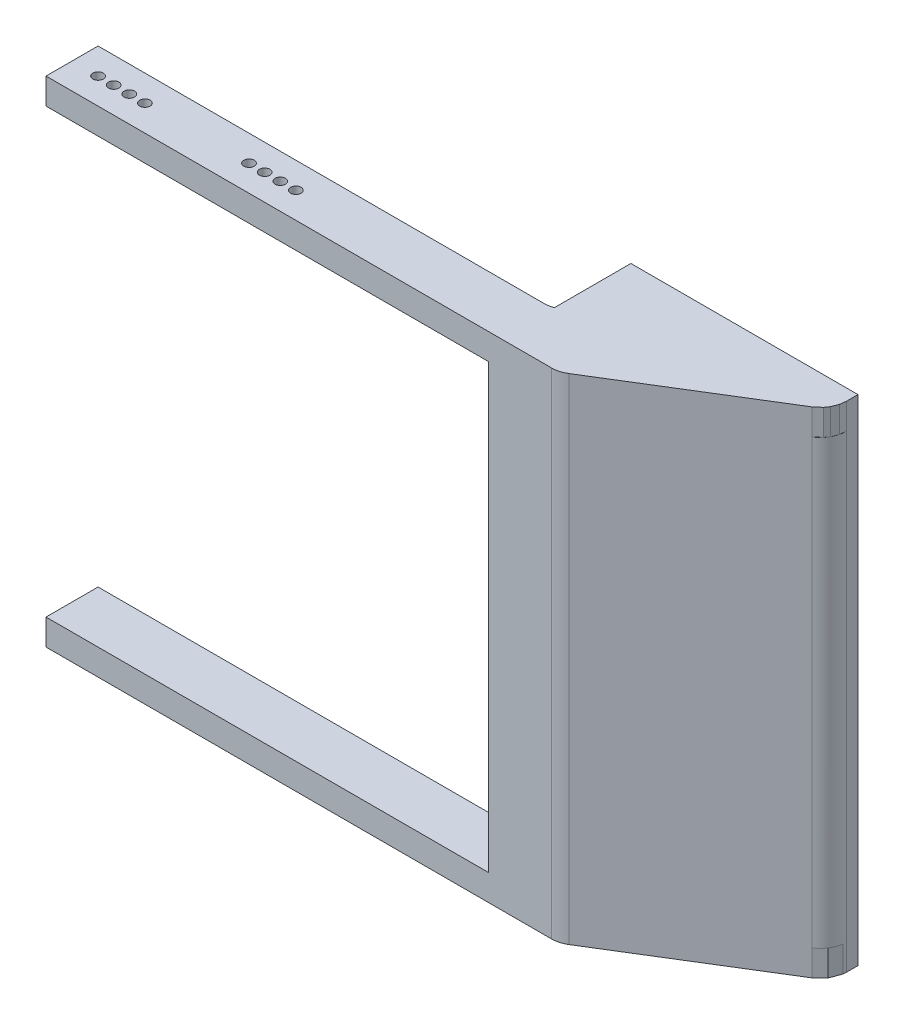
SolidWorks part; units mm, degrees
other "Marquage1"
sketch "Esquisse6" plane through (-75, 0, -38.2843) normal (-0.024, -0.0063, -0.9997) x (-0.9942, -0.1051, 0.0245)
ref_plane "Front Plane" through (0, 0, 0) normal (0, 0, 1) x (1, 0, 0)
ref_plane "Top Plane" through (0, 0, 0) normal (0, 1, 0) x (1, 0, 0)
ref_plane "Right Plane" through (0, 0, 0) normal (1, 0, 0) x (0, 0, -1)
sketch "Sketch1" plane through (0, 0, 0) normal (0, 1, 0) x (1, 0, 0)
  line L0 (-55, 0) -> (55, 0) construction
  line L1 (30, 0) -> (-75, 0)
  line L4 (-75, 0) -> (-75, 10)
  line L5 (30, 10) -> (55.9808, 25)
  line L6 (55.9808, 25) -> (55.9808, 20)
  line L7 (55.9808, 20) -> (28.4498, 3.0365)
  line L8 (30, 10) -> (12.5, 25)
  line L9 (12.5, 25) -> (12.5, 20)
  line L10 (12.5, 20) -> (24.1667, 10)
  line L11 (28.4498, 3.0365) -> (23.5217, 0)
  line L12 (-75, 10) -> (24.1667, 10)
  line L13 (23.5217, 0) -> (-75, 0)
  line L14 (24.1667, 10) -> (30, 10)
  dimension "D10" = 10
  dimension "D1" = 30
  dimension "D2" = 30
  dimension "D3" = 75
  dimension "D4" = 10
  dimension "D5" = 20
  dimension "D6" = 30
  dimension "D7" = 5
  dimension "D8" = 20
  dimension "D9" = 5
  dimension "D11" = 109.399
extrude "Boss-Extrude3" add sketch "Sketch1" along normal blind 95 contours L4 L12 L10 L9 L8 L5 L6 L7 L11 L13
fillet "Fillet8" radius 5 1 edges at (24.1667, 47.5, -10)
fillet "Fillet9" radius 5 2 edges at (55.9808, 47.5, -20) (12.5, 47.5, -20)
fillet "Fillet10" radius 5 1 edges at (23.5217, 47.5, 0)
sketch "Esquisse3" plane through (0, 0, -10) normal (0, 0, -1) x (-1, 0, 0)
  line L0 (75, 95) -> (75, 0) construction
  line L1 (75, 5) -> (45, 5)
  line L2 (75, 5) -> (75, 90)
  line L3 (75, 90) -> (45, 90)
  line L4 (45, 5) -> (45, 90)
  line L5 (75, 0) -> (-10.6504, 0) construction
  line L6 (75, 95) -> (-10.6504, 95) construction
  dimension "D1" = 5
  dimension "D2" = 5
  dimension "D3" = 30
extrude "Enlèv. mat.-Extru.1" cut sketch "Esquisse3" against normal through all contours L2 L1 L4 L3
sketch "Esquisse5" plane through (0, 0, -10) normal (0, 0, -1) x (-1, 0, 0)
  line L1 (45, 5) -> (35, 5)
  line L2 (45, 5) -> (45, 65)
  line L3 (45, 65) -> (35, 65)
  line L4 (35, 5) -> (35, 65)
  dimension "D1" = 10
extrude "Enlèv. mat.-Extru.2" cut sketch "Esquisse5" against normal through all contours L2 L1 L4 L3
sketch "Esquisse14" plane through (0, 0, -10) normal (0, 0, -1) x (-1, 0, 0)
  line L0 (45, 65) -> (35, 65) construction
  line L1 (45, 90) -> (35, 90)
  line L2 (45, 90) -> (45, 65)
  line L3 (45, 65) -> (35, 65)
  line L4 (35, 90) -> (35, 65)
extrude "Enlèv. mat.-Extru.7" cut sketch "Esquisse14" against normal through all
sketch "Esquisse15" plane through (0, 0, -10) normal (0, 0, -1) x (-1, 0, 0)
  line L1 (35, 90) -> (5, 90)
  line L2 (35, 90) -> (35, 5)
  line L3 (35, 5) -> (5, 5)
  line L4 (5, 90) -> (5, 5)
  dimension "D1" = 30
extrude "Enlèv. mat.-Extru.8" cut sketch "Esquisse15" against normal through all
sketch "Esquisse21" plane through (0, 0, -10) normal (0, 0, -1) x (-1, 0, 0)
  line L1 (5, 90) -> (-10, 90)
  line L2 (5, 90) -> (5, 5)
  line L3 (5, 5) -> (-10, 5)
  line L4 (-10, 90) -> (-10, 5)
  dimension "D1" = 15
extrude "Enlèv. mat.-Extru.9" cut sketch "Esquisse21" against normal through all
sketch "Esquisse61" plane through (0, 0, 0) normal (0, 1, 0) x (1, 0, 0)
  line L1 (12.2705, 25) -> (55.9406, 25)
  line L2 (12.2705, 25) -> (12.2705, 4.0617)
  line L3 (12.2705, 4.0617) -> (55.9406, 4.0617)
  line L4 (55.9406, 25) -> (55.9406, 4.0617)
extrude "Boss.-Extru.3" add sketch "Esquisse61" along normal blind 5
sketch "Esquisse63" plane through (0, 5, 0) normal (0, 1, 0) x (1, 0, 0)
  line L0 (55.9406, 22.16) -> (55.183, 20.0827)
  line L1 (55.183, 20.0827) -> (53.6036, 18.5353)
  line L2 (53.6036, 18.5353) -> (30.1137, 4.0617)
  line L3 (30.1137, 4.0617) -> (55.9406, 4.0617)
  line L4 (55.9406, 4.0617) -> (55.9406, 22.16)
  arc A0 (53.6036, 18.5353) -> (55.9406, 22.16) centre (50.9808, 22.7921) ccw construction
extrude "Enlèv. mat.-Extru.18" cut sketch "Esquisse63" against normal blind 5
sketch "Esquisse69" plane through (0, 95, 0) normal (0, 1, 0) x (1, 0, 0)
  line L1 (55.9808, 25) -> (12.3569, 25)
  line L2 (55.9808, 25) -> (55.9808, 7.8571)
  line L3 (55.9808, 7.8571) -> (12.3569, 7.8571)
  line L4 (12.3569, 25) -> (12.3569, 7.8571)
extrude "Boss.-Extru.4" add sketch "Esquisse69" against normal blind 5
sketch "Esquisse71" plane through (0, 90, 0) normal (0, -1, 0) x (1, 0, 0)
  line L0 (55.9808, -22.7921) -> (55.8261, -21.5582)
  line L1 (55.8261, -21.5582) -> (55.3462, -20.3543)
  line L2 (55.3462, -20.3543) -> (54.8122, -19.5797)
  line L3 (54.8122, -19.5797) -> (53.6036, -18.5353)
  line L4 (53.6036, -18.5353) -> (36.2734, -7.8571)
  line L5 (36.2734, -7.8571) -> (55.9808, -7.8571)
  line L6 (55.9808, -7.8571) -> (55.9808, -22.7921)
  arc A0 (55.9808, -22.7921) -> (53.6036, -18.5353) centre (50.9808, -22.7921) ccw construction
extrude "Enlèv. mat.-Extru.21" cut sketch "Esquisse71" against normal blind 10
sketch "Esquisse77" plane through (3.1699, 0, 5.4904) normal (-0.5, 0, -0.866) x (-0.866, 0, 0.5)
  line L0 (-30.9808, 90) -> (-40.9808, 90)
  line L1 (-60.9808, 90) -> (-30.9808, 90) construction
  line L2 (-40.9808, 90) -> (-31.4808, 5)
  line L3 (-30.9808, 5) -> (-60.9344, 5) construction
  line L4 (-31.4808, 5) -> (-30.9808, 5)
  line L5 (-30.9808, 90) -> (-30.9808, 5) construction
  line L6 (-30.9808, 5) -> (-30.9808, 90)
  dimension "D1" = 0.5
  dimension "D2" = 10
extrude "Boss.-Extru.7" add sketch "Esquisse77" along normal blind 17
sketch "Esquisse79" plane through (0, 90, 0) normal (0, 1, 0) x (1, 0, 0)
  line L0 (21.9808, 25) -> (32.8868, 25)
  line L1 (32.8868, 25) -> (30.1603, 29.7224)
  line L2 (30.1603, 29.7224) -> (21.9808, 25)
extrude "Enlèv. mat.-Extru.25" cut sketch "Esquisse79" against normal up to next and the other way through all
sketch "Esquisse80" plane through (0, 5, 0) normal (0, 1, 0) x (1, 0, 0)
  line L3 (12.5, 25) -> (30, 10)
  line L4 (30, 10) -> (21.25, 25)
  line L5 (55.9406, 25) -> (12.5, 25) construction
  line L6 (21.25, 25) -> (12.5, 25)
extrude "Boss.-Extru.10" add sketch "Esquisse80" along normal blind 86
sketch "Esquisse84" plane through (0, 90, 0) normal (0, -1, 0) x (-1, 0, 0)
  line L0 (75, 0) -> (75, 10) construction
  line L1 (75, 0) -> (-10, 0) construction
  circle A0 centre (70, 5) radius 1
  circle A1 centre (67, 5) radius 1
  circle A2 centre (64, 5) radius 1
  circle A3 centre (61, 5) radius 1
  circle A4 centre (41, 5) radius 1
  circle A5 centre (38, 5) radius 1
  circle A6 centre (35, 5) radius 1
  circle A7 centre (32, 5) radius 1
  dimension "D2" = 2
  dimension "D1" = 5
  dimension "D3" = 5
  dimension "D4" = 3
  dimension "D5" = 3
  dimension "D6" = 3
  dimension "D7" = 20
  dimension "D8" = 3
  dimension "D9" = 3
  dimension "D10" = 3
extrude "Enlèv. mat.-Extru.26" cut sketch "Esquisse84" against normal through all
ref_plane "Plan1" through (55.9808, 0, -25) normal (0, -1, 0) x (-1, 0, 0)
sketch "Esquisse92" plane through (3.1699, 0, 5.4904) normal (-0.5, 0, -0.866) x (-0.866, 0, 0.5)
  line L0 (-60.9353, 0) -> (-60.9808, 14.9866)
  line L1 (-85.7308, 0) -> (-36.2308, 0) construction
  line L2 (-60.9808, 90) -> (-60.9808, 0) construction
  line L3 (-60.9808, 14.9866) -> (-32.5969, 14.9866)
  line L4 (-40.9808, 90) -> (-31.4808, 5) construction
  line L5 (-60.9808, 14.9866) -> (-60.9808, 24.9866)
  line L6 (-60.9808, 24.9866) -> (-33.7146, 24.9866)
  line L7 (-60.9808, 24.9866) -> (-60.9808, 54.9866)
  line L8 (-60.9808, 54.9866) -> (-37.0675, 54.9866)
  line L9 (-60.9808, 54.9866) -> (-60.9808, 64.9866)
  line L10 (-60.9808, 64.9866) -> (-38.1851, 64.9866)
